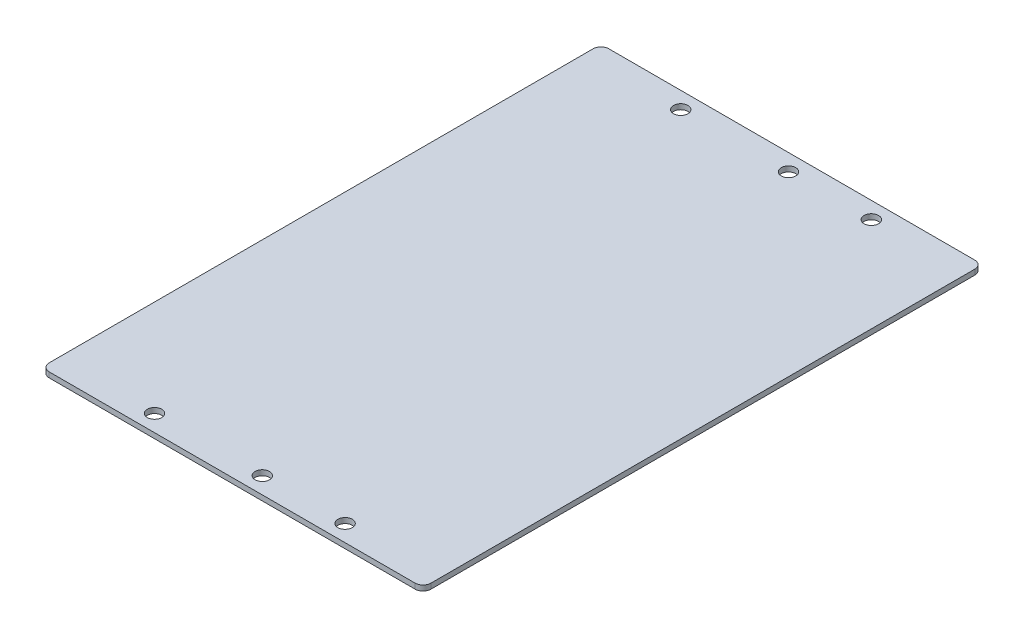
SolidWorks part; units mm, degrees
material "Zoltek Panex 33"
ref_plane "Front Plane" through (0, 0, 0) normal (0, 0, 1) x (1, 0, 0)
ref_plane "Top Plane" through (0, 0, 0) normal (0, 1, 0) x (1, 0, 0)
ref_plane "Right Plane" through (0, 0, 0) normal (1, 0, 0) x (0, 0, -1)
sketch "Sketch1" plane through (0, 0, 0) normal (0, 1, 0) x (1, 0, 0)
  line L0 (138.9, 214.3) -> (138.9, 202.3) construction
  line L5 (18.4, 202.3) -> (18.4, 214.3) construction
  line L6 (136.9, 1.405) -> (20.4, 1.405) construction
  line L7 (83.4, 163.4515) -> (83.4, 52.2535) construction
  line L8 (43.9375, 107.8525) -> (122.8625, 107.8525) construction
  line L9 (5.7, 1.405) -> (150.9, 1.405)
  line L10 (5.7, 1.405) -> (5.7, 214.3)
  line L11 (5.7, 214.3) -> (150.9, 214.3)
  line L12 (150.9, 1.405) -> (150.9, 214.3)
  line L13 (136.9, 214.3) -> (20.4, 214.3) construction
  line L14 (150.9, -29.595) -> (150.9, 246) construction
  line L15 (18.4, 1.405) -> (18.4, 13.405) construction
  circle A0 centre (42.4, 207.95) radius 2.75
  circle A1 centre (83.4, 207.95) radius 2.75
  circle A2 centre (114.9, 207.95) radius 2.75
  circle A3 centre (114.9, 7.755) radius 2.75
  circle A4 centre (83.4, 7.755) radius 2.75
  circle A5 centre (42.4, 7.755) radius 2.75
  dimension "D4" = 5.5
  dimension "D5" = 24
  dimension "D6" = 24
  dimension "D7" = 0
  dimension "D2" = 6.35
  dimension "D1" = 12.7
extrude "Boss-Extrude1" add sketch "Sketch1" along normal blind 2
fillet "Fillet1" radius 3 4 edges at (5.7, 1, -214.3) (150.9, 1, -214.3) (150.9, 1, -1.405) (5.7, 1, -1.405)
